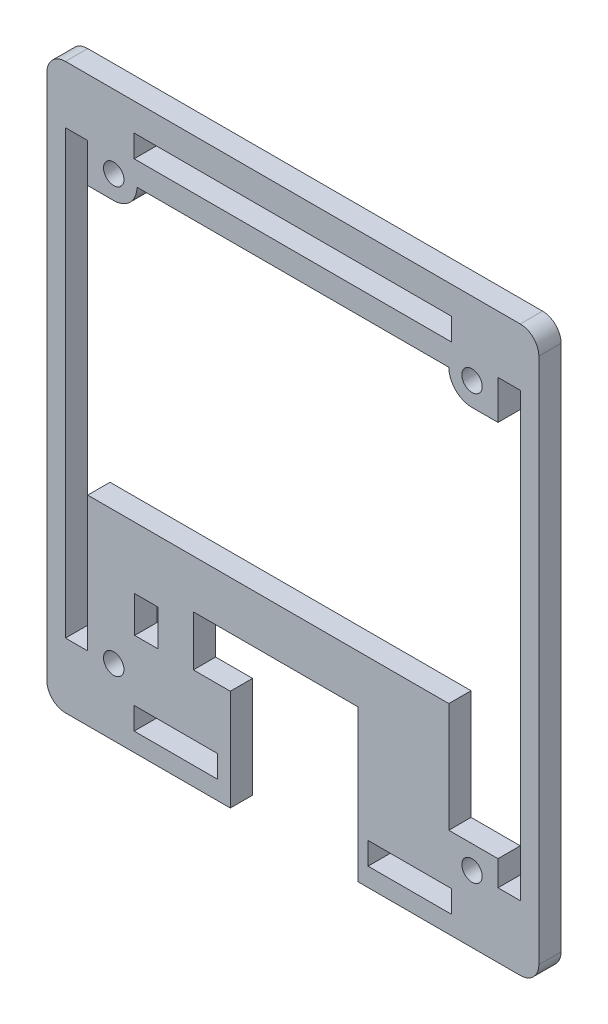
SolidWorks part; units mm, degrees
ref_plane "Front Plane" through (0, 0, 0) normal (0, 0, 1) x (1, 0, 0)
ref_plane "Top Plane" through (0, 0, 0) normal (0, 1, 0) x (1, 0, 0)
ref_plane "Right Plane" through (0, 0, 0) normal (1, 0, 0) x (0, 0, -1)
sketch "Sketch1" plane through (0, 0, 0) normal (0, 0, 1) x (1, 0, 0)
  line L3 (1.8034, 3.2766) -> (0, 3.2766) construction
  line L12 (57.9374, 3.2766) -> (59.7408, 3.2766) construction
  line L14 (57.9374, 3.2766) -> (57.9374, 63.754) construction
  line L15 (57.9374, 63.754) -> (59.7408, 63.754) construction
  line L16 (51.5874, 66.5734) -> (51.5874, 64.77) construction
  line L19 (8.1534, 66.5734) -> (8.1534, 64.77) construction
  line L20 (1.8034, 63.754) -> (-1.2446, 63.754)
  line L21 (-1.2446, 63.754) -> (-1.2446, 3.2766)
  line L22 (1.8034, 63.754) -> (1.8034, 3.2766)
  line L23 (1.8034, 3.2766) -> (-1.2446, 3.2766)
  line L24 (19.5834, -3.048) -> (19.5834, 0)
  line L25 (19.5834, -3.048) -> (8.1534, -3.048)
  line L26 (8.1534, -3.048) -> (8.1534, 0)
  line L27 (19.5834, 0) -> (8.1534, 0)
  line L28 (40.1574, -3.048) -> (40.1574, 0)
  line L29 (51.5874, -3.048) -> (40.1574, -3.048)
  line L30 (51.5874, 0) -> (40.1574, 0)
  line L31 (51.5874, -3.048) -> (51.5874, 0)
  line L32 (57.9374, 3.2766) -> (60.9854, 3.2766)
  line L33 (60.9854, 3.2766) -> (60.9854, 63.754)
  line L34 (57.9374, 3.2766) -> (57.9374, 63.754)
  line L35 (57.9374, 63.754) -> (60.9854, 63.754)
  line L36 (51.5874, 67.818) -> (51.5874, 64.77)
  line L37 (8.1534, 64.77) -> (51.5874, 64.77)
  line L38 (8.1534, 67.818) -> (51.5874, 67.818)
  line L39 (8.1534, 67.818) -> (8.1534, 64.77)
  line L40 (57.9374, 6.731) -> (51.2064, 6.731)
  line L41 (-3.7846, -5.588) -> (63.5254, -5.588)
  line L42 (-3.7846, -5.588) -> (-3.7846, 71.6116)
  line L43 (-3.7846, 71.6116) -> (63.5254, 71.6116)
  line L44 (63.5254, -5.588) -> (63.5254, 71.6116)
  line L45 (5.3594, 58.42) -> (1.8034, 58.42) construction
  line L46 (54.3814, 58.42) -> (57.9374, 58.42) construction
  line L47 (5.3594, 58.42) -> (1.8034, 58.42)
  line L48 (54.3814, 58.42) -> (57.9374, 58.42)
  line L49 (8.5344, 61.595) -> (51.2064, 61.595)
  line L50 (1.8034, 3.2766) -> (1.8034, 21.7424)
  line L51 (1.8034, 21.7424) -> (51.2064, 21.7424)
  line L52 (57.9374, 21.7424) -> (57.9374, 3.2766)
  line L53 (21.3106, -4.3434) -> (21.3106, -5.588)
  line L54 (1.8034, 21.7424) -> (1.8034, 3.2766)
  line L55 (57.9374, 21.7424) -> (57.9374, 3.2766)
  line L56 (51.2064, 6.731) -> (51.2064, 21.7424)
  line L57 (38.7858, -4.3434) -> (38.7858, -5.588)
  circle A0 centre (54.3814, 61.595) radius 1.397 construction
  circle A1 centre (5.3594, 61.595) radius 1.397 construction
  circle A2 centre (54.3814, 61.595) radius 1.397
  circle A3 centre (5.3594, 61.595) radius 1.397
  arc A8 (5.3594, 58.42) -> (5.3594, 64.77) centre (5.3594, 61.595) ccw construction
  arc A9 (54.3814, 64.77) -> (54.3814, 58.42) centre (54.3814, 61.595) ccw construction
  arc A10 (5.3594, 58.42) -> (5.3594, 64.77) centre (5.3594, 61.595) ccw
  arc A11 (54.3814, 64.77) -> (54.3814, 58.42) centre (54.3814, 61.595) ccw
  line B0 (8.2296, 13.2842) -> (11.4046, 13.2842)
  line B1 (8.2296, 13.2842) -> (8.2296, 8.3312)
  line B2 (11.4046, 13.2842) -> (11.4046, 8.3312)
  line B3 (8.2296, 8.3312) -> (11.4046, 8.3312)
  line B4 (16.256, 15.1384) -> (16.256, 8.255)
  line B5 (16.256, 8.255) -> (21.3106, 8.255)
  line B6 (38.7858, 15.1384) -> (16.256, 15.1384)
  line B7 (38.7858, -4.3434) -> (38.7858, 15.1384)
  line B8 (21.3106, 8.255) -> (21.3106, -4.3434)
  circle B9 centre (5.3594, 3.556) radius 1.397
  circle B10 centre (54.3814, 3.556) radius 1.397
  dimension "D1" = 3.048
  dimension "D2" = 6.604
  dimension "D3" = 3.048
  dimension "D4" = 6.731
  dimension "D5" = 77.1996
  dimension "D6" = 67.31
  dimension "D7" = 3.7936
sketch_block_instance "Block1-1"
sketch_block "Block1"
extrude "Boss-Extrude1" add sketch "Sketch1" along normal blind 3.048 contours B8 B5 B4 B6 B7 B10 B9 B3 B1 B0 B2 L31 L29 L28 L30 L27 L24 L25 L26 L39 L38 L36 L37 A2 A3 A11 L48 L34 L35 L33 L32 region at (-2.7604, 33.0118, 0)
fillet "Fillet1" radius 2.54 4 edges at (-3.7846, -5.588, 1.524) (63.5254, -5.588, 1.524) (63.5254, 71.6116, 1.524) (-3.7846, 71.6116, 1.524)
